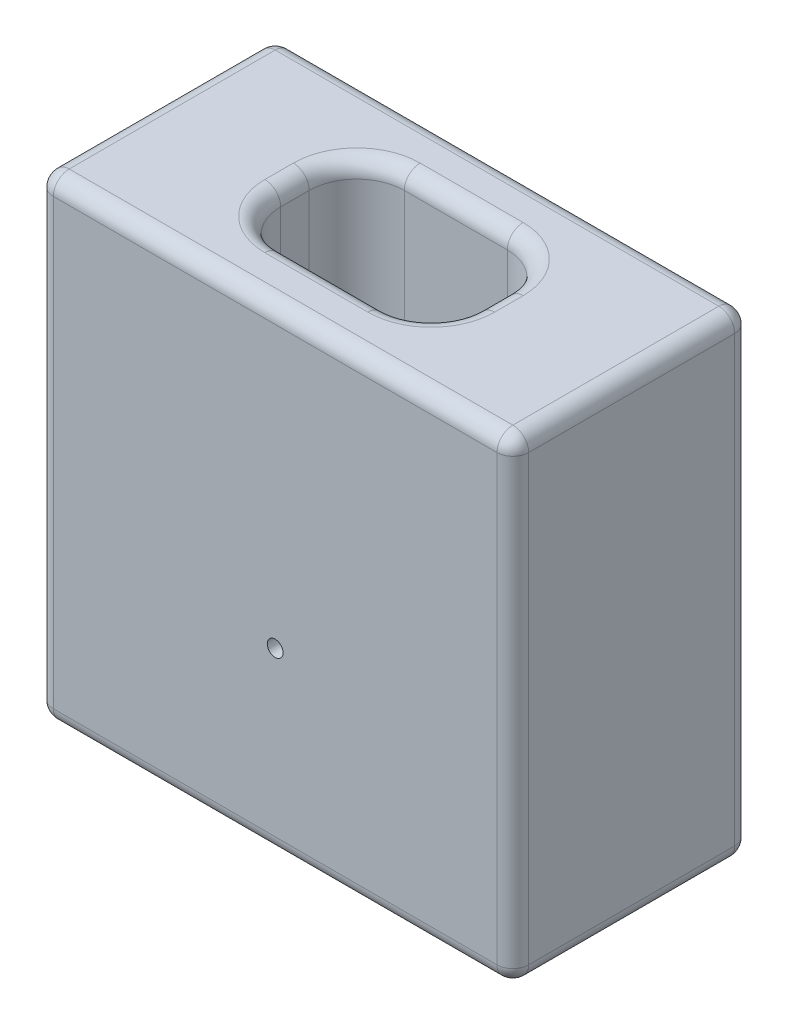
SolidWorks part; units mm, degrees
ref_plane "Front Plane" through (0, 0, 0) normal (0, 0, 1) x (1, 0, 0)
ref_plane "Top Plane" through (0, 0, 0) normal (0, 1, 0) x (1, 0, 0)
ref_plane "Right Plane" through (0, 0, 0) normal (1, 0, 0) x (0, 0, -1)
sketch "Sketch1" plane through (0, 0, 0) normal (0, 1, 0) x (1, 0, 0)
  line L1 (-19.05, -9.525) -> (19.05, -9.525)
  line L2 (-19.05, -9.525) -> (-19.05, 9.525)
  line L3 (-19.05, 9.525) -> (19.05, 9.525)
  line L4 (19.05, -9.525) -> (19.05, 9.525)
  line L5 (-19.05, -9.525) -> (19.05, 9.525) construction
  line L6 (-19.05, 9.525) -> (19.05, -9.525) construction
  point P0 (0, 0)
  dimension "D1" = 38.1
  dimension "D2" = 19.05
extrude "Boss-Extrude1" add sketch "Sketch1" along normal blind 12.7
sketch "Sketch2" plane through (0, 12.7, 0) normal (0, 1, 0) x (1, 0, 0)
  line L0 (-7.9375, 9.525) -> (-7.9375, -9.525)
  line L1 (19.05, 9.525) -> (-19.05, 9.525) construction
  line L2 (-19.05, -9.525) -> (19.05, -9.525) construction
  line L3 (7.9375, 9.525) -> (7.9375, -9.525)
  line L4 (-7.9375, 0) -> (-19.05, 0) construction
  line L5 (-19.05, 9.525) -> (-19.05, -9.525) construction
  line L6 (7.9375, 0) -> (19.05, 0) construction
  line L7 (19.05, -9.525) -> (19.05, 9.525) construction
  line L8 (-7.9375, -4.953) -> (7.9375, -4.953)
  line L9 (-7.9375, 4.953) -> (7.9375, 4.953)
  line L10 (0, -4.953) -> (0, -9.525) construction
  line L11 (0, 4.953) -> (0, 9.525) construction
  line L13 (-4.064, -4.064) -> (4.064, -4.064)
  line L14 (-4.064, -4.064) -> (-4.064, 4.064)
  line L15 (-4.064, 4.064) -> (4.064, 4.064)
  line L16 (4.064, -4.064) -> (4.064, 4.064)
  line L17 (-4.064, -4.064) -> (4.064, 4.064) construction
  line L18 (-4.064, 4.064) -> (4.064, -4.064) construction
  point P24 (0, 0)
  line M9 (19.05, -9.525) -> (19.05, 9.525)
  line M10 (19.05, 9.525) -> (-19.05, 9.525)
  line M11 (-19.05, 9.525) -> (-19.05, -9.525)
  line M12 (-19.05, -9.525) -> (19.05, -9.525)
  dimension "D1" = 15.875
  dimension "D2" = 9.906
  dimension "D4" = 8.128
extrude "Boss-Extrude2" add sketch "Sketch2" along normal blind 25.4 contours L0 L9 L3 M10 | L0 M10 M11 M12 | L3 M10 M12 M9 | L8 L0 L3 M12 region at (0, 12.7, -7.239) region at (-13.4937, 12.7, 0) region at (13.4938, 12.7, 0) region at (0, 12.7, 7.239)
extrude "Boss-Extrude3" add sketch "Sketch2<3>" along normal blind 10.16 contours L13 L16 L15 L14 region at (0, 12.7, 0)
sketch "Sketch2<3>" plane through (0, 12.7, 0) normal (0, 1, 0) x (1, 0, 0) same geometry as "Sketch2"
fillet "Fillet1" radius 1.905 4 edges at (-4.064, 17.78, 4.064) (4.064, 17.78, 4.064) (4.064, 17.78, -4.064) (-4.064, 17.78, -4.064)
sketch "Sketch3" plane through (0, 0, -9.525) normal (0, 0, -1) x (-1, 0, 0)
  line L0 (0, 14.351) -> (0, 12.7) construction
  line L4 (-7.9375, 12.7) -> (7.9375, 12.7)
  line L5 (-7.9375, 38.1) -> (-7.9375, 12.7)
  line L6 (7.9375, 38.1) -> (-7.9375, 38.1)
  line L7 (7.9375, 12.7) -> (7.9375, 38.1)
  line L8 (-7.9375, 12.7) -> (7.9375, 12.7) construction
  line L9 (-7.9375, 38.1) -> (-7.9375, 12.7) construction
  line L10 (7.9375, 38.1) -> (-7.9375, 38.1) construction
  line L11 (7.9375, 12.7) -> (7.9375, 38.1) construction
  circle A0 centre (0, 14.351) radius 0.635
  dimension "D2" = 1.27
  dimension "D3" = 1.651
  dimension "D1" = 0
extrude "Cut-Extrude1" cut sketch "Sketch3" against normal through all
fillet "Fillet2" radius 3.81 4 edges at (7.9375, 25.4, 4.953) (7.9375, 25.4, -4.953) (-7.9375, 25.4, 4.953) (-7.9375, 25.4, -4.953)
sketch "Sketch4" plane through (0, 0, -9.525) normal (0, 0, -1) x (-1, 0, 0)
  line L0 (-5.08, 14.351) -> (-5.08, 0)
  line L1 (-19.05, 0) -> (19.05, 0) construction
  line L2 (5.08, 14.351) -> (5.08, 0)
  line L3 (5.08, 0) -> (-5.08, 0)
  circle A0 centre (0, 14.351) radius 0.635 construction
  circle A1 centre (0, 14.351) radius 0.635 construction
  circle A2 centre (0, 14.351) radius 5.08
  circle M3 centre (0, 14.351) radius 0.635
  line M4 (-19.05, 0) -> (19.05, 0)
  dimension "D1" = 10.16
extrude "Boss-Extrude4" add sketch "Sketch4" along normal blind 6.35 contours A2 M3 | A2 L0 L2 M4 region at (0, 5.2426, -9.525) region at (0, 19.2873, -9.525)
fillet "Fillet3" radius 1.27 38 edges at (-12.065, 0, -9.525) (12.065, 0, -9.525) (0, 0, 9.525) (19.05, 19.05, 9.525) (19.05, 19.05, -9.525) (19.05, 0, 0) (-19.05, 19.05, -9.525) (-19.05, 19.05, 9.525) (-19.05, 0, 0) (6.8216, 38.1, 3.8371) (7.9375, 38.1, 0) (6.8216, 38.1, -3.8371) (0, 38.1, -4.953) (-6.8216, 38.1, -3.8371) (-7.9375, 38.1, 0) (-6.8216, 38.1, 3.8371) (0, 38.1, 4.953) (0, 38.1, -9.525) (19.05, 38.1, 0) (0, 38.1, 9.525) (-19.05, 38.1, 0) (-3.506, 22.86, -3.506) (0, 22.86, -4.064) (3.506, 22.86, -3.506) (4.064, 22.86, 0) (3.506, 22.86, 3.506) (0, 22.86, 4.064) (-3.506, 22.86, 3.506) (-4.064, 22.86, 0) (5.08, 0, -12.7) (0, 0, -15.875) (-5.08, 0, -12.7) (-5.08, 7.1755, -15.875) (0, 19.431, -15.875) (-5.08, 7.1755, -9.525) (0, 19.431, -9.525) (5.08, 7.1755, -15.875) (5.08, 7.1755, -9.525)
